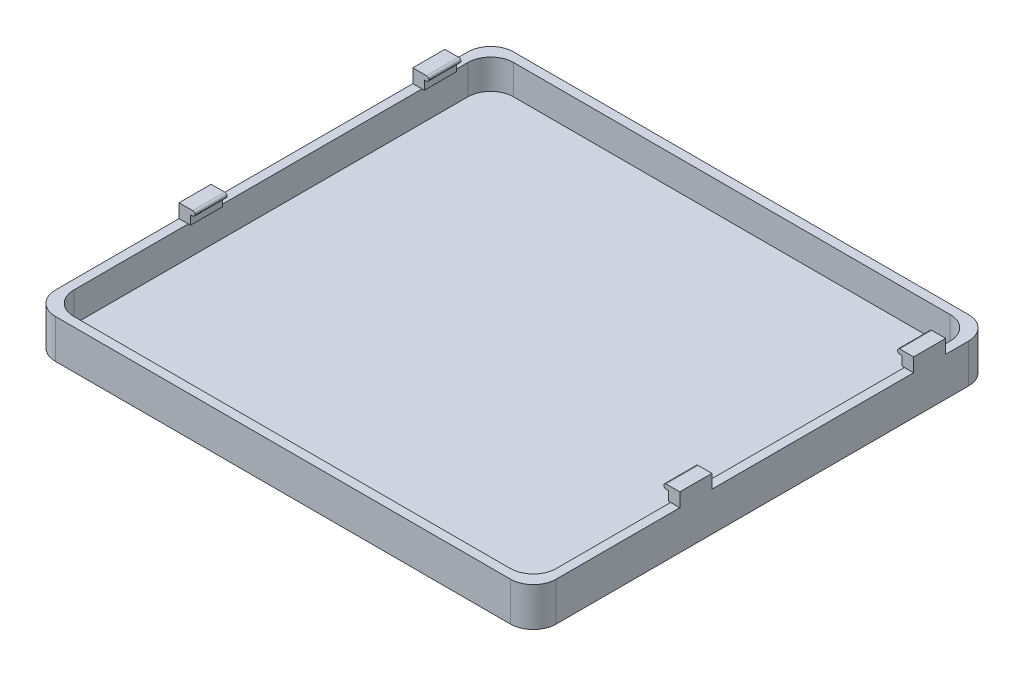
SolidWorks part; units mm, degrees
ref_plane "Front Plane" through (0, 0, 0) normal (0, 0, 1) x (1, 0, 0)
ref_plane "Top Plane" through (0, 0, 0) normal (0, 1, 0) x (1, 0, 0)
ref_plane "Right Plane" through (0, 0, 0) normal (1, 0, 0) x (0, 0, -1)
sketch "Sketch1" plane through (0, 0, 0) normal (0, 1, 0) x (1, 0, 0)
  line L1 (-54.65, 0) -> (54.65, 0)
  line L2 (-54.65, 0) -> (-54.65, -100)
  line L3 (-54.65, -100) -> (54.65, -100)
  line L4 (54.65, 0) -> (54.65, -100)
  point P4 (0, 0)
  dimension "D1" = 109.3
  dimension "D2" = 100
extrude "Boss-Extrude1" add sketch "Sketch1" along normal blind 8.5
sketch "Sketch2" plane through (0, 8.5, 0) normal (0, 1, 0) x (1, 0, 0)
  line L0 (-54.65, 0) -> (-54.65, -100) construction
  line L1 (-54.65, -10) -> (-52.15, -10)
  line L2 (-54.65, -10) -> (-54.65, -17)
  line L3 (-54.65, -17) -> (-52.15, -17)
  line L4 (-52.15, -10) -> (-52.15, -17)
  line L5 (54.65, 0) -> (-54.65, 0) construction
  line L6 (0, -55) -> (0, 55) construction
  line L7 (52.15, -10) -> (52.15, -17)
  line L8 (54.65, -17) -> (52.15, -17)
  line L9 (54.65, -10) -> (54.65, -17)
  line L10 (54.65, -10) -> (52.15, -10)
  line L11 (-70.5487, -39.01) -> (75.6401, -39.01) construction
  line L12 (54.65, 0) -> (-54.65, 0) construction
  line L13 (54.65, -68.02) -> (52.15, -68.02)
  line L14 (54.65, -68.02) -> (54.65, -61.02)
  line L15 (54.65, -61.02) -> (52.15, -61.02)
  line L16 (52.15, -68.02) -> (52.15, -61.02)
  line L17 (-52.15, -68.02) -> (-52.15, -61.02)
  line L18 (-54.65, -61.02) -> (-52.15, -61.02)
  line L19 (-54.65, -68.02) -> (-54.65, -61.02)
  line L20 (-54.65, -68.02) -> (-52.15, -68.02)
  dimension "D1" = 10
  dimension "D2" = 7
  dimension "D3" = 2.5
  dimension "D4" = 39.01
extrude "Boss-Extrude2" add sketch "Sketch2" along normal blind 3
sketch "Sketch3" plane through (-52.15, 0, 0) normal (1, 0, 0) x (0, 0, -1)
  line L0 (-10, 11.5) -> (-10, 8.5) construction
  line L1 (-17, 11.5) -> (-10, 11.5)
  line L2 (-17, 11.5) -> (-17, 10.5)
  line L3 (-17, 10.5) -> (-10, 10.5)
  line L4 (-10, 11.5) -> (-10, 10.5)
  line L5 (-61.02, 11.5) -> (-61.02, 8.5) construction
  line L6 (-68.02, 11.5) -> (-61.02, 11.5)
  line L7 (-68.02, 11.5) -> (-68.02, 10.5)
  line L8 (-68.02, 10.5) -> (-61.02, 10.5)
  line L9 (-61.02, 11.5) -> (-61.02, 10.5)
  dimension "D1" = 1
  dimension "D2" = 1
extrude "Boss-Extrude3" add sketch "Sketch3" along normal blind 1
sketch "Sketch4" plane through (52.15, 0, 0) normal (-1, 0, 0) x (0, 0, 1)
  line L1 (10, 11.5) -> (17, 11.5)
  line L2 (10, 11.5) -> (10, 10.5)
  line L3 (10, 10.5) -> (17, 10.5)
  line L4 (17, 11.5) -> (17, 10.5)
  line L6 (61.02, 11.5) -> (68.02, 11.5)
  line L7 (61.02, 11.5) -> (61.02, 10.5)
  line L8 (61.02, 10.5) -> (68.02, 10.5)
  line L9 (68.02, 11.5) -> (68.02, 10.5)
  line L10 (17, 11.5) -> (17, 8.5) construction
  line L12 (68.02, 11.5) -> (68.02, 8.5) construction
  dimension "D1" = 1
  dimension "D2" = 1
extrude "Boss-Extrude4" add sketch "Sketch4" along normal blind 1
fillet "Fillet1" radius 0.5 8 edges at (51.15, 11.5, 13.5) (51.15, 10.5, 13.5) (51.15, 10.5, 64.52) (51.15, 11.5, 64.52) (-51.15, 10.5, 13.5) (-51.15, 11.5, 13.5) (-51.15, 10.5, 64.52) (-51.15, 11.5, 64.52)
sketch "Sketch5" plane through (0, 8.5, 0) normal (0, 1, 0) x (1, 0, 0)
  line L0 (54.65, -61.02) -> (54.65, -17) construction
  line L1 (-52.65, -2) -> (52.65, -2)
  line L2 (-52.65, -2) -> (-52.65, -98)
  line L3 (-52.65, -98) -> (52.65, -98)
  line L4 (52.65, -2) -> (52.65, -98)
  line L5 (-54.65, -17) -> (-54.65, -61.02) construction
  line L6 (54.65, 0) -> (-54.65, 0) construction
  line L7 (-54.65, -100) -> (54.65, -100) construction
  dimension "D1" = 2
  dimension "D2" = 2
  dimension "D3" = 2
  dimension "D4" = 2
extrude "Cut-Extrude1" cut sketch "Sketch5" against normal offset from surface (6.5 mm away) 2 up to face at (0, 0, 50)
fillet "Fillet2" radius 5 8 edges at (54.65, 4.25, 0) (-54.65, 4.25, 0) (-54.65, 4.25, 100) (54.65, 4.25, 100) (52.65, 5.25, 98) (-52.65, 5.25, 98) (52.65, 5.25, 2) (-52.65, 5.25, 2)
